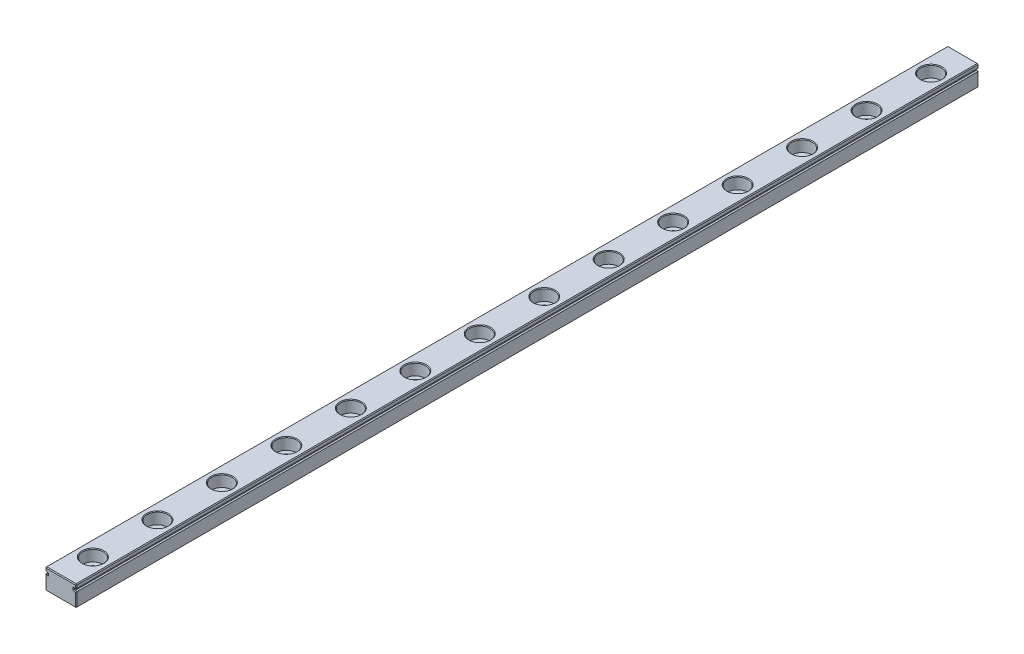
SolidWorks part; units mm, degrees
material "1.4401 (X5CrNiMo17-12-2)"
ref_plane "Front Plane" through (0, 0, 0) normal (0, 0, 1) x (1, 0, 0)
ref_plane "Top Plane" through (0, 0, 0) normal (0, 1, 0) x (1, 0, 0)
ref_plane "Right Plane" through (0, 0, 0) normal (1, 0, 0) x (0, 0, -1)
sketch "Sketch1" plane through (0, 0, 0) normal (0, 0, 1) x (1, 0, 0)
  line L0 (0, 0) -> (0, 8) construction
  line L1 (0, 8) -> (12, 8)
  line L2 (0, 0) -> (12, 0)
  line L3 (0, 8) -> (0, 6.75)
  line L4 (0, 6.75) -> (0.5, 6.25) construction
  line L5 (0.5, 6.25) -> (1, 6.25)
  line L6 (0.5, 5.75) -> (0, 5.25) construction
  line L7 (0, 5.25) -> (0, 0)
  line L8 (1, 6.25) -> (1, 5.75)
  line L9 (1, 5.75) -> (0.5, 5.75)
  line L10 (0.5, 5.75) -> (0.75, 6) construction
  line L11 (0.75, 6) -> (0.5, 6.25) construction
  line L12 (0, 6.75) -> (0, 6.559)
  line L13 (0, 5.25) -> (0, 5.441)
  line L14 (6, 8) -> (6, 0) construction
  line L15 (11.25, 6) -> (11.5, 6.25) construction
  line L16 (11.5, 5.75) -> (11.25, 6) construction
  line L17 (11.5, 5.75) -> (12, 5.25) construction
  line L18 (12, 6.75) -> (11.5, 6.25) construction
  line L19 (12, 0) -> (12, 8) construction
  line L20 (12, 5.25) -> (12, 5.441)
  line L21 (12, 6.75) -> (12, 6.559)
  line L22 (11, 5.75) -> (11.5, 5.75)
  line L23 (11, 6.25) -> (11, 5.75)
  line L24 (12, 5.25) -> (12, 0)
  line L25 (11.5, 6.25) -> (11, 6.25)
  line L26 (12, 8) -> (12, 6.75)
  arc A0 (0, 5.441) -> (0.5, 5.75) centre (0, 6) ccw
  arc A1 (0.5, 6.25) -> (0, 6.559) centre (0, 6) ccw
  arc A2 (11.5, 6.25) -> (12, 6.559) centre (12, 6) cw
  arc A3 (12, 5.441) -> (11.5, 5.75) centre (12, 6) cw
  point P4 (1, 6)
  point P28 (11, 6)
  dimension "D1" = 8
  dimension "D2" = 6
  dimension "D3" = 0.5
  dimension "D4" = 45
  dimension "D5" = 2
  dimension "D6" = 1
extrude "Boss-Extrude1" add sketch "Sketch1" along normal blind 350
chamfer "Chamfer1" distance 0.3 angle 45 36 edges at (0, 0, 175) (12, 0, 175) (0, 8, 175) (12, 8, 175) (0.2939, 5.5245, 350) (0.75, 5.75, 350) (1, 6, 350) (0.75, 6.25, 350) (0.2939, 6.4755, 350) (0, 7.2795, 350) (6, 8, 350) (12, 7.2795, 350) (11.7061, 6.4755, 350) (11.25, 6.25, 350) (11, 6, 350) (11.25, 5.75, 350) (11.7061, 5.5245, 350) (12, 2.7205, 350) (6, 0, 350) (0, 2.7205, 350) (12, 2.7205, 0) (11.7061, 5.5245, 0) (11.25, 5.75, 0) (11, 6, 0) (11.25, 6.25, 0) (11.7061, 6.4755, 0) (12, 7.2795, 0) (6, 0, 0) (0, 2.7205, 0) (0.2939, 5.5245, 0) (0.75, 5.75, 0) (1, 6, 0) (0.75, 6.25, 0) (0.2939, 6.4755, 0) (0, 7.2795, 0) (6, 8, 0)
hole_wizard "CBORE for M5 Hex Head Bolt1" positions "3DSketch1" profile "Sketch3" counterbore size "M5" standard "ANSI Metric" end condition through all
sketch3d "3DSketch1"
  line L0 (6, 8, 0) -> (6, 8, 12.5) construction
  line L1 (11.7, 8, 0) -> (0.3, 8, 0) construction
  point P0 (6, 8, 12.5)
  dimension "D1" = 12.5
sketch "Sketch3" plane through (6, 8, 12.5) normal (1, 0, 0) x (0, 0, 1)
  line L0 (0, 0) -> (0, 8)
  line L1 (2.25, 7.75) -> (2.5, 8)
  line L2 (4, 4.5) -> (2.25, 4.5)
  line L3 (2.25, 4.5) -> (2.25, 7.75)
  line L5 (4, 4.5) -> (4, 0.25)
  line L6 (4, 0.25) -> (4.25, 0)
  line L7 (4.25, 0) -> (0, 0)
  line L8 (-4, 0.25) -> (-4.25, 0) construction
  line L11 (0, -6.35) -> (0, 107.95) construction
  line L12 (2.5, 8) -> (0, 8)
  line L13 (-2.25, 7.75) -> (-2.5, 8) construction
  dimension "Thru Hole Dia." = 4.5
  dimension "Thru Hole Depth" = 8
  dimension "C'Bore Dia." = 8
  dimension "C'Bore Depth" = 4.5
  dimension "Near C'Sink Dia." = 8.5
  dimension "Near C'Sink Angle" = 90
  dimension "Far C'Sink Dia." = 5
  dimension "Far C'Sink Angle" = 90
pattern_linear "LPattern1" count 14 spacing 25 along (0, 0, 1) of "CBORE for M5 Hex Head Bolt1"
